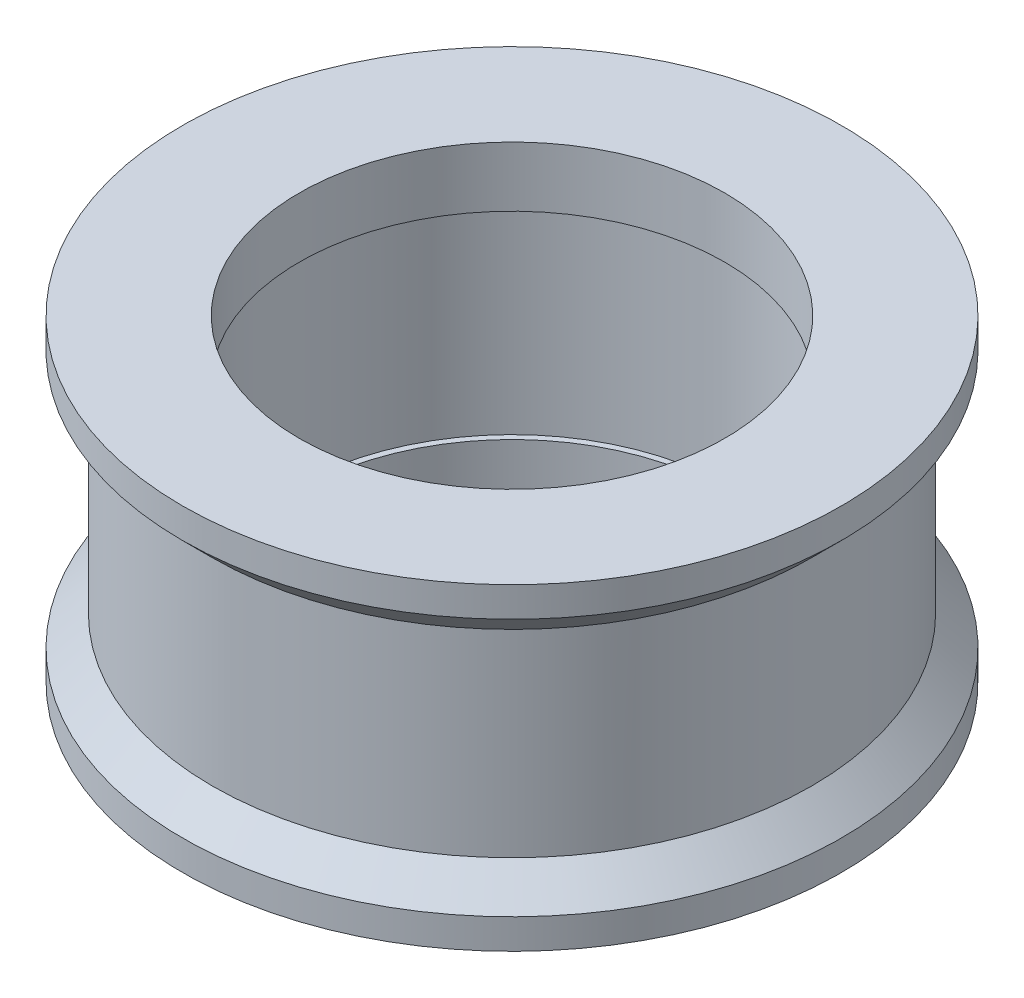
SolidWorks part; units mm, degrees
ref_plane "前视基准面" through (0, 0, 0) normal (0, 0, 1) x (1, 0, 0)
ref_plane "上视基准面" through (0, 0, 0) normal (0, 1, 0) x (1, 0, 0)
ref_plane "右视基准面" through (0, 0, 0) normal (1, 0, 0) x (0, 0, -1)
sketch "草图1" plane through (0, 0, 0) normal (0, 1, 0) x (1, 0, 0)
  circle A0 centre (0, 0) radius 3.65
  circle A1 centre (0, 0) radius 5
  dimension "D1" = 7.3
  dimension "D2" = 10
extrude "凸台-拉伸1" add sketch "草图1" along normal blind 3.3
sketch "草图2" plane through (0, 0, 0) normal (0, -1, 0) x (1, 0, 0)
  circle A0 centre (0, 0) radius 5.5
  circle A1 centre (0, 0) radius 3.55
  dimension "D1" = 11
  dimension "D2" = 7.1
extrude "凸台-拉伸2" add sketch "草图2" along normal blind 1
sketch "草图3" plane through (0, 3.3, 0) normal (0, 1, 0) x (1, 0, 0)
  circle A0 centre (0, 0) radius 3.55
  circle A1 centre (0, 0) radius 5.5
  dimension "D1" = 11
  dimension "D2" = 7.1
extrude "凸台-拉伸3" add sketch "草图3" along normal blind 1
chamfer "倒角1" distance 0.5 angle 45 2 edges at (0, 3.3, 5.5) (0, 0, -5.5)
